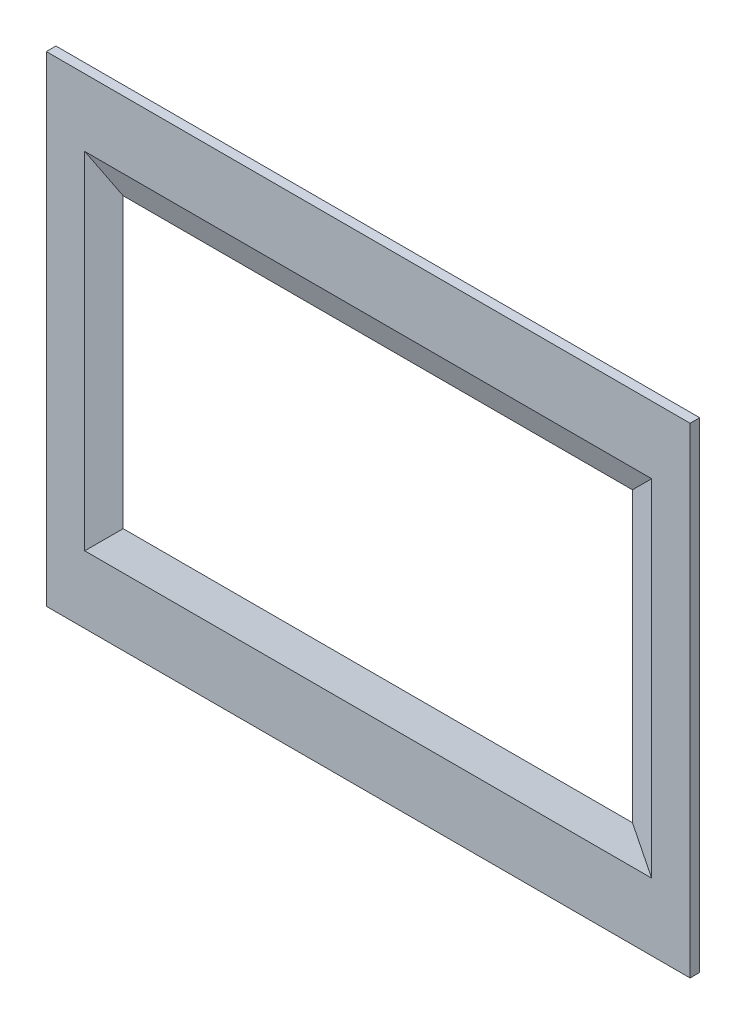
SolidWorks part; units mm, degrees
ref_plane "Front Plane" through (0, 0, 0) normal (0, 0, 1) x (1, 0, 0)
ref_plane "Top Plane" through (0, 0, 0) normal (0, 1, 0) x (1, 0, 0)
ref_plane "Right Plane" through (0, 0, 0) normal (1, 0, 0) x (0, 0, -1)
sketch "Sketch1" plane through (0, 0, 0) normal (0, 0, 1) x (1, 0, 0)
  line L1 (0, 0) -> (670, 0)
  line L2 (0, 0) -> (0, 500)
  line L3 (0, 500) -> (670, 500)
  line L4 (670, 0) -> (670, 500)
  line L5 (70, 400) -> (600, 400)
  line L6 (70, 400) -> (70, 100)
  line L7 (70, 100) -> (600, 100)
  line L8 (600, 400) -> (600, 100)
  dimension "D1" = 670
  dimension "D2" = 500
  dimension "D3" = 100
  dimension "D4" = 300
  dimension "D5" = 530
  dimension "D6" = 70
  dimension "D7" = 70
  dimension "D8" = 100
extrude "Extrude1" add sketch "Sketch1" along normal blind 10
chamfer "Chamfer1" distance 30 distance2 10 1 edges at (335, 400, 10) first distance on face at (335, 250, 10)
chamfer "Chamfer2" distance 30 distance2 10 1 edges at (70, 265, 10) first distance on face at (335, 250, 10)
chamfer "Chamfer3" distance 30 distance2 10 1 edges at (320, 100, 10) first distance on face at (335, 250, 10)
chamfer "Chamfer4" distance 30 distance2 10 1 edges at (600, 250, 10) first distance on face at (335, 250, 10)
